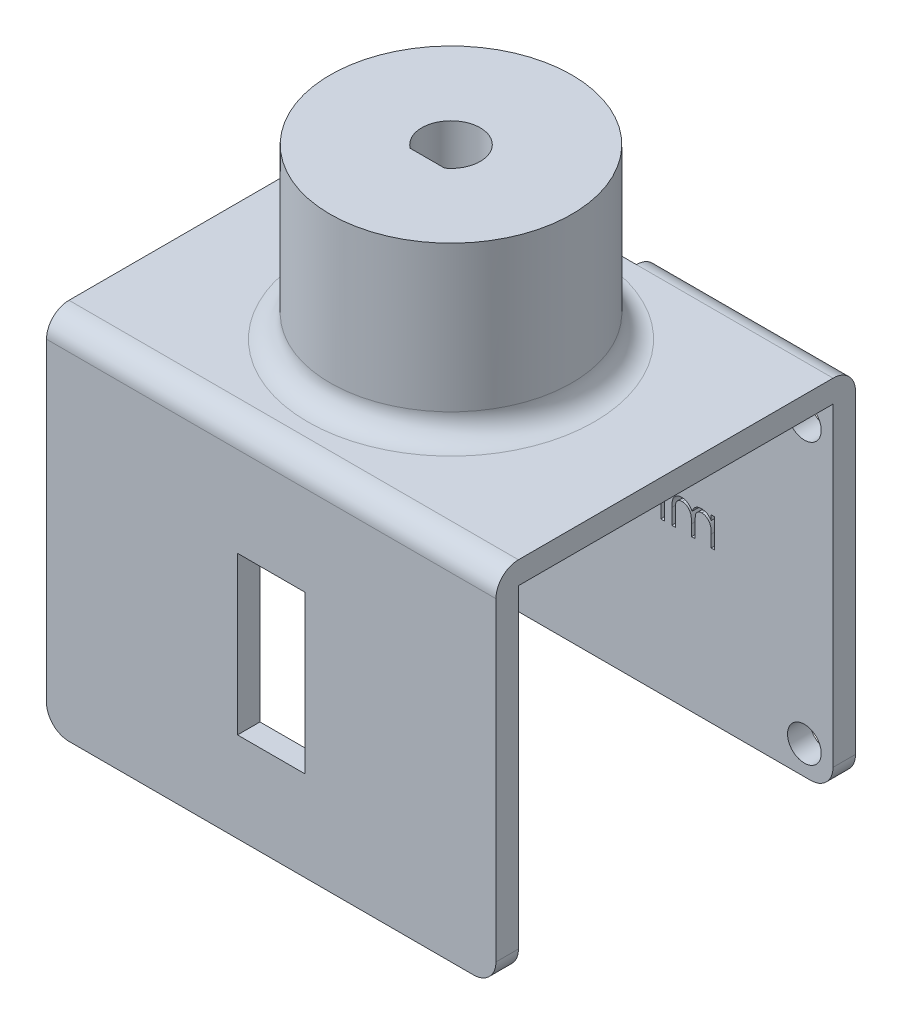
SolidWorks part; units mm, degrees
ref_plane "Front Plane" through (0, 0, 0) normal (0, 0, 1) x (1, 0, 0)
ref_plane "Top Plane" through (0, 0, 0) normal (0, 1, 0) x (1, 0, 0)
ref_plane "Right Plane" through (0, 0, 0) normal (1, 0, 0) x (0, 0, -1)
sketch "Sketch1" plane through (0, 0, 0) normal (0, 1, 0) x (1, 0, 0)
  line L1 (20, 16) -> (-20, 16)
  line L2 (20, 16) -> (20, -16)
  line L3 (20, -16) -> (-20, -16)
  line L4 (-20, 16) -> (-20, -16)
  line L5 (20, 16) -> (-20, -16) construction
  line L6 (20, -16) -> (-20, 16) construction
  point P0 (0, 0)
  dimension "D1" = 40
  dimension "D2" = 32
extrude "Boss-Extrude1" add sketch "Sketch1" along normal blind 2
sketch "Sketch2" plane through (0, 2, 0) normal (0, 1, 0) x (1, 0, 0)
  circle A0 centre (0, 0) radius 10.75
  dimension "D1" = 21.5
extrude "Boss-Extrude2" add sketch "Sketch2" along normal blind 15 contours A0
sketch "Sketch3" plane through (0, 0, 0) normal (0, -1, 0) x (1, 0, 0)
  circle A0 centre (0, 0) radius 8.5
  dimension "D1" = 17
extrude "Cut-Extrude1" cut sketch "Sketch3" against normal offset from surface (9.5 mm away) 9.5 up to face at (0, 0, 0)
sketch "Sketch5" plane through (0, 0, 0) normal (0, 0, 1) x (1, 0, 0)
  line L0 (-10.75, 17) -> (-10.75, 2) construction
  line L1 (-10.75, 9.5) -> (-6.4271, 9.5)
  line L2 (-10.75, 9.5) -> (-10.75, 4)
  line L3 (-10.75, 4) -> (-6.4271, 4)
  line L4 (-6.4271, 9.5) -> (-6.4271, 4)
  line L5 (-20, 2) -> (20, 2) construction
  dimension "D1" = 2
sketch "Sketch7" plane through (0, 0, 0) normal (0, 0, 1) x (1, 0, 0)
  line L0 (0, 0) -> (0, 17) construction
  line L1 (10.75, 17) -> (-10.75, 17) construction
revolve "Cut-Revolve1" cut sketch "Sketch5" angle 90 about L0
fillet "Fillet1" radius 2 1 edges at (0, 2, 10.75)
sketch "Sketch8" plane through (0, 0, 0) normal (0, -1, 0) x (1, 0, 0)
  line L0 (20, 16) -> (20, -16) construction
  line L1 (-20, -16) -> (20, -16)
  line L2 (-20, -16) -> (-20, -14)
  line L3 (-20, -14) -> (20, -14)
  line L4 (20, -16) -> (20, -14)
  line L5 (55, 0) -> (-55, 0) construction
  line L6 (-20, 14) -> (20, 14)
  line L7 (20, 16) -> (20, 14)
  line L8 (-20, 16) -> (20, 16)
  line L9 (-20, 16) -> (-20, 14)
  dimension "D1" = 2
sketch "Sketch9" plane through (0, 17, 0) normal (0, 1, 0) x (1, 0, 0)
  line L0 (-1.533, -2.1) -> (1.533, -2.1)
  arc A0 (1.533, -2.1) -> (-1.533, -2.1) centre (0, 0) ccw
  dimension "D2" = 5.2
  dimension "D1" = 2.1
extrude "Cut-Extrude2" cut sketch "Sketch9" against normal up to next
extrude "Boss-Extrude3" add sketch "Sketch8" along normal blind 30
sketch "Sketch10" plane through (0, 0, -16) normal (0, 0, -1) x (-1, 0, 0)
  line L0 (0, 17.6) -> (0, -17.6) construction
  line L1 (-21, -15) -> (21, -15) construction
  line L2 (-20, 2) -> (-20, -30) construction
  line L3 (20, 2) -> (20, -30) construction
  line L4 (-20, 2) -> (20, 2) construction
  line L5 (-20, 0) -> (20, 0) construction
  line L6 (2.5, 2) -> (-2.5, 2)
  line L7 (2.5, 2) -> (2.5, -4)
  line L8 (2.5, -4) -> (-2.5, -4)
  line L9 (-2.5, 2) -> (-2.5, -4)
  line L10 (2.5, 2) -> (-2.5, -4) construction
  line L11 (2.5, -4) -> (-2.5, 2) construction
  line L12 (-20, 2) -> (20, 2) construction
  circle A0 centre (-17.45, -2.55) radius 1.5
  circle A1 centre (17.45, -2.55) radius 1.5
  circle A2 centre (17.45, -27.45) radius 1.5
  circle A3 centre (-17.45, -27.45) radius 1.5
  text T0 "miao 2.0"
  point P18 (0, -1)
  dimension "D7" = 3
  dimension "D1" = 2.55
  dimension "D2" = 2.55
  dimension "D3" = 6
  dimension "D4" = 5
  dimension "D5" = 2
  dimension "D6" = 15
extrude "Cut-Extrude3" cut sketch "Sketch10" against normal offset from surface (2 mm away) 2 up to face at (0, -14, -16)
fillet "Fillet2" radius 2 7 edges at (-11.25, 2, -16) (0, 2, 16) (-20, -30, 15) (20, -30, 15) (20, -30, -15) (-20, -30, -15) (11.25, 2, -16)
sketch "Sketch11" plane through (0, 0, 16) normal (0, 0, 1) x (1, 0, 0)
  line L0 (0, -17.6) -> (0, 17.6) construction
  line L1 (-3, -22) -> (3, -22)
  line L2 (-3, -22) -> (-3, -8)
  line L3 (-3, -8) -> (3, -8)
  line L4 (3, -22) -> (3, -8)
  line L5 (-3, -22) -> (3, -8) construction
  line L6 (-3, -8) -> (3, -22) construction
  line L7 (20, 0) -> (-20, 0) construction
  line L8 (18, -30) -> (-18, -30) construction
  point P0 (0, -15)
  dimension "D1" = 8
  dimension "D2" = 8
  dimension "D3" = 6
extrude "Cut-Extrude4" cut sketch "Sketch11" against normal blind 10
